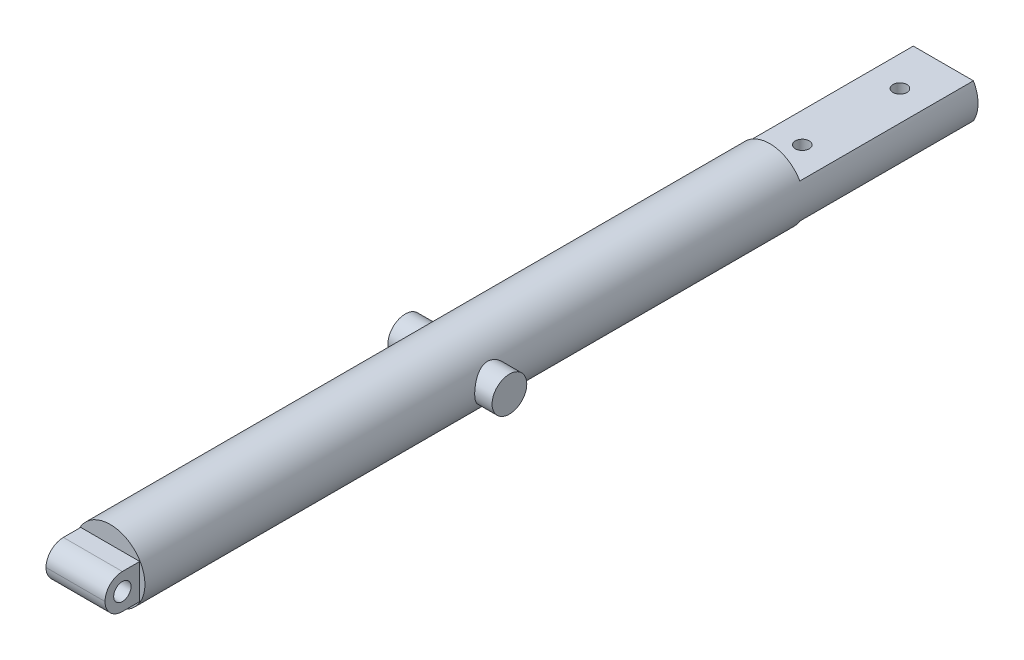
SolidWorks part; units mm, degrees
ref_plane "Front Plane" through (0, 0, 0) normal (0, 0, 1) x (1, 0, 0)
ref_plane "Top Plane" through (0, 0, 0) normal (0, 1, 0) x (1, 0, 0)
ref_plane "Right Plane" through (0, 0, 0) normal (1, 0, 0) x (0, 0, -1)
sketch "Sketch1" plane through (0, 0, 0) normal (0, 0, 1) x (1, 0, 0)
  circle A0 centre (0, 0) radius 12.7
sketch "Sketch9" plane through (0, 0, 0) normal (1, 0, 0) x (0, 0, -1)
  line L0 (0, 0) -> (-25.4, 0) construction
  circle A0 centre (-25.4, 0) radius 6.35
extrude "Boss-Extrude3" add sketch "Sketch1" along normal mid plane 304.8 contours A0
ref_plane "Plane1" through (0, -6.35, 0) normal (0, 1, 0) x (1, 0, 0)
extrude "Boss-Extrude6" add sketch "Sketch9" along normal mid plane 38.1
ref_plane "Plane2" through (0, -6.35, 0) normal (0, 1, 0) x (1, 0, 0)
sketch "Sketch16" plane through (0, -6.35, 0) normal (0, 1, 0) x (1, 0, 0)
  line L0 (0, 0) -> (0, 152.4) construction
  line L1 (12.7, 152.4) -> (-12.7, 152.4) construction
  line L2 (0, 152.4) -> (-12.7, 152.4) construction
  line L3 (12.7, -19.0501) -> (12.7, 152.4) construction
  line L4 (-12.7, 152.4) -> (12.7, 152.4)
  line L5 (-12.7, 152.4) -> (-12.7, 88.9)
  line L6 (-12.7, 88.9) -> (12.7, 88.9)
  line L7 (12.7, 152.4) -> (12.7, 88.9)
extrude "Cut-Extrude2" cut sketch "Sketch16" against normal through all contours L5 L6 L7 L4
ref_plane "Plane3" through (0, 6.35, 0) normal (0, 1, 0) x (1, 0, 0)
sketch "Sketch17" plane through (0, 6.35, 0) normal (0, 1, 0) x (1, 0, 0)
  line L0 (12.7, -19.0501) -> (12.7, 152.4) construction
  line L1 (-12.7, 152.4) -> (12.7, 152.4)
  line L2 (-12.7, 152.4) -> (-12.7, 88.9)
  line L3 (-12.7, 88.9) -> (12.7, 88.9)
  line L4 (12.7, 152.4) -> (12.7, 88.9)
extrude "Cut-Extrude3" cut sketch "Sketch17" along normal through all
sketch "Sketch19" plane through (0, 6.35, 0) normal (0, 1, 0) x (1, 0, 0)
  line L0 (0, 88.9) -> (0, 100.8062) construction
  line L1 (-10.9985, 88.9) -> (10.9985, 88.9) construction
  line L2 (0, 103.3462) -> (0, 132.5562) construction
  line L3 (0, 132.5562) -> (0, 136.525) construction
  line L4 (10.9985, 88.9) -> (-10.9985, 88.9) construction
  line L5 (10.9985, 88.9) -> (-10.9985, 88.9) construction
  circle A0 centre (0, 100.8062) radius 2.54
  circle A1 centre (0, 136.525) radius 2.54
  dimension "D1" = 47.625
  dimension "D2" = 11.9063
extrude "Cut-Extrude5" cut sketch "Sketch19" against normal through all
sketch "Sketch20" plane through (0, -6.35, 0) normal (0, -1, 0) x (1, 0, 0)
  line L0 (0, -88.9) -> (0, -100.8062) construction
  line L1 (-10.9985, -88.9) -> (10.9985, -88.9) construction
  line L2 (0, -88.9) -> (0, -136.525) construction
  circle A0 centre (0, -100.8062) radius 2.54
  circle A1 centre (0, -136.525) radius 2.54
sketch "Sketch21" plane through (0, 0, 152.4) normal (0, 0, 1) x (1, 0, 0)
  line L9 (-10.795, 6.35) -> (10.795, 6.35)
  line L10 (-10.795, 6.35) -> (-10.795, -6.35)
  line L11 (-10.795, -6.35) -> (10.795, -6.35)
  line L12 (10.795, 6.35) -> (10.795, -6.35)
  line L13 (-10.795, 6.35) -> (10.795, -6.35) construction
  line L14 (-10.795, -6.35) -> (10.795, 6.35) construction
  point P0 (0, 0)
extrude "Boss-Extrude8" add sketch "Sketch21" along normal blind 12.7 contours L10 L11 L12 L9
sketch "Sketch25" plane through (-10.795, 0, 0) normal (-1, 0, 0) x (0, 0, 1)
  circle A0 centre (158.75, 0) radius 3.175
sketch "Sketch27" plane through (0, 0, 0) normal (0, 1, 0) x (1, 0, 0)
  line L0 (0, -165.1) -> (0, -165.354) construction
  line L1 (-10.795, -165.1) -> (10.795, -165.1) construction
  line L2 (0, -165.354) -> (11.049, -165.354)
  line L3 (0, -165.354) -> (-11.049, -165.354)
  line L4 (-11.049, -165.354) -> (-11.049, -152.654)
  line L6 (11.049, -165.354) -> (11.049, -152.654)
  line L7 (-11.049, -152.654) -> (-21.209, -152.654)
  line L8 (11.049, -152.654) -> (21.209, -152.654)
  line L9 (-21.209, -152.654) -> (-21.209, -170.434)
  line L10 (-21.209, -170.434) -> (21.209, -170.434)
  line L11 (21.209, -170.434) -> (21.209, -152.654)
extrude "Boss-Extrude9" add sketch "Sketch27" along normal mid plane 12.7 separate body
sketch "Sketch29" plane through (-21.209, 0, 0) normal (-1, 0, 0) x (0, 0, 1)
  circle A0 centre (158.8279, 0) radius 2.921
extrude "Cut-Extrude7" cut sketch "Sketch25" against normal up to next (21.59 mm away)
extrude "Boss-Extrude10" add sketch "Sketch29" against normal blind 35.814
fillet "Fillet2" radius 6.35 4 edges at (16.129, -6.35, 152.654) (16.129, 6.35, 152.654) (-16.129, -6.35, 152.654) (-16.129, 6.35, 152.654)
fillet "Fillet3" radius 6.35 2 edges at (0, -6.35, 165.1) (0, 6.35, 165.1)
sketch "Sketch31" plane through (0, 0, 170.434) normal (0, 0, 1) x (1, 0, 0)
  line L1 (31.75, -31.75) -> (-31.75, -31.75)
  line L2 (31.75, -31.75) -> (31.75, 31.75)
  line L3 (31.75, 31.75) -> (-31.75, 31.75)
  line L4 (-31.75, -31.75) -> (-31.75, 31.75)
  line L5 (31.75, -31.75) -> (-31.75, 31.75) construction
  line L6 (31.75, 31.75) -> (-31.75, -31.75) construction
  point P0 (0, 0)
extrude "Boss-Extrude11" add sketch "Sketch31" along normal blind 10.16
sketch "Sketch32" plane through (0, 31.75, 0) normal (0, 1, 0) x (1, 0, 0)
  line L5 (-39.1953, -165.354) -> (37.3309, -165.354)
  line L6 (-39.1953, -165.354) -> (-39.1953, -182.7698)
  line L7 (-39.1953, -182.7698) -> (37.3309, -182.7698)
  line L8 (37.3309, -165.354) -> (37.3309, -182.7698)
extrude "Cut-Extrude8" cut sketch "Sketch32" against normal through all
sketch "Sketch33" plane through (0, 6.35, 0) normal (0, 1, 0) x (1, 0, 0)
  line L1 (-21.209, -152.654) -> (-11.049, -152.654)
  line L2 (-21.209, -152.654) -> (-21.209, -165.354)
  line L3 (-21.209, -165.354) -> (-11.049, -165.354)
  line L4 (-11.049, -152.654) -> (-11.049, -165.354)
  line L5 (11.049, -152.654) -> (21.209, -152.654)
  line L6 (11.049, -152.654) -> (11.049, -165.354)
  line L7 (11.049, -165.354) -> (21.209, -165.354)
  line L8 (21.209, -152.654) -> (21.209, -165.354)
extrude "Cut-Extrude9" cut sketch "Sketch33" against normal through all
sketch "Sketch35" plane through (-10.795, 0, 0) normal (-1, 0, 0) x (0, 0, 1)
  circle A1 centre (158.8279, 0) radius 2.921
extrude "Cut-Extrude11" cut sketch "Sketch35" against normal through all both and the other way through all
